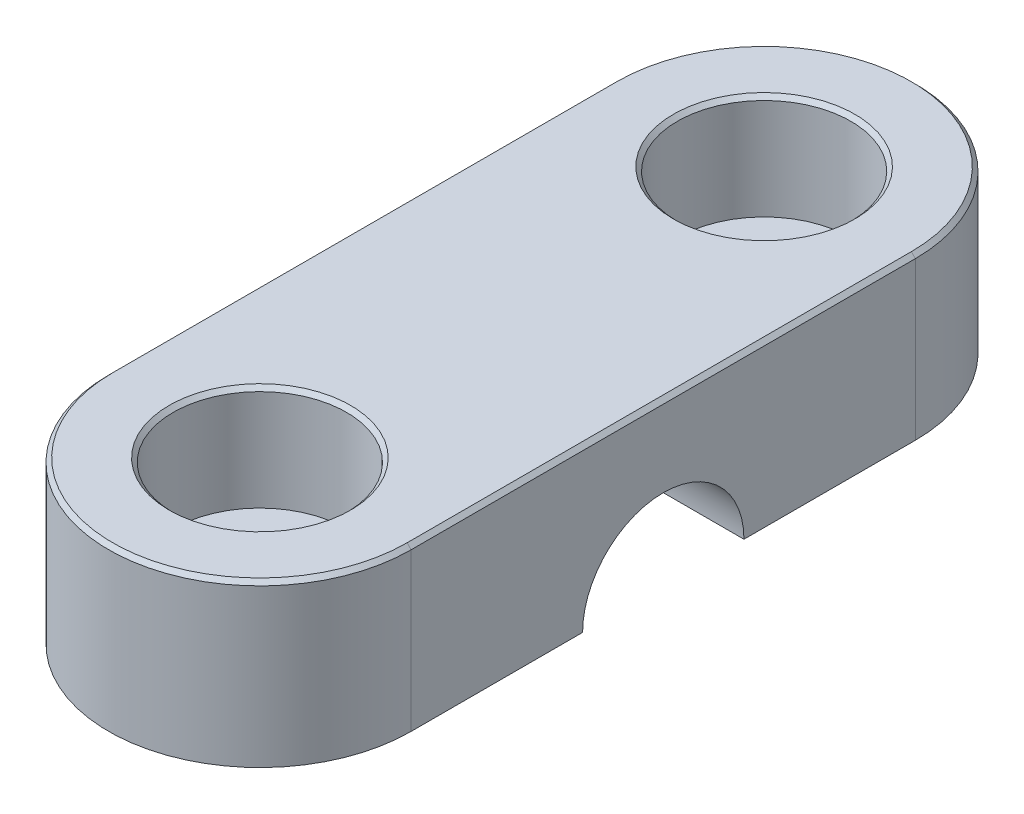
SolidWorks part; units mm, degrees
ref_plane "Front Plane" through (0, 0, 0) normal (0, 0, 1) x (1, 0, 0)
ref_plane "Top Plane" through (0, 0, 0) normal (0, 1, 0) x (1, 0, 0)
ref_plane "Right Plane" through (0, 0, 0) normal (1, 0, 0) x (0, 0, -1)
sketch "Sketch1" plane through (0, 0, 0) normal (0, 1, 0) x (1, 0, 0)
  line L0 (0, 20) -> (0, -20) construction
  line L1 (-7.5, 20) -> (7.5, 20)
  line L2 (-7.5, 20) -> (-7.5, -20)
  line L3 (-7.5, -20) -> (7.5, -20)
  line L4 (7.5, 20) -> (7.5, -20)
  line L5 (-7.5, 20) -> (7.5, -20) construction
  line L6 (-7.5, -20) -> (7.5, 20) construction
  line L7 (-7.5, 0) -> (7.5, 0) construction
  circle A0 centre (0, 12.5) radius 7.5
  circle A1 centre (0, 12.5) radius 2.6
  circle A2 centre (0, -12.5) radius 2.6
  circle A3 centre (0, -12.5) radius 7.5
  point P0 (0, 0)
  dimension "D3" = 5.2
  dimension "D1" = 15
  dimension "D2" = 40
extrude "Boss-Extrude1" add sketch "Sketch1" along normal blind 8 contours A0 A1 | L2 A3 L4 A0 | A3 A2 region at (5.1533, 0, -17.6533) region at (0, 0, 0) region at (0, 0, 5.2121)
sketch "Sketch2" plane through (7.5, 0, 0) normal (1, 0, 0) x (0, 0, -1)
  circle A0 centre (0, 0) radius 4
  point P2 (0, 0)
  point P4 (0, 0)
  dimension "D1" = 8
extrude "Cut-Extrude1" cut sketch "Sketch2" against normal up to next
sketch "Sketch3" plane through (0, 8, 0) normal (0, 1, 0) x (1, 0, 0)
  circle A0 centre (0, 12.5) radius 4.3
  circle A1 centre (0, -12.5) radius 4.3
  dimension "D1" = 8.6
extrude "Cut-Extrude2" cut sketch "Sketch3" against normal blind 5.2
chamfer "Chamfer1" distance 0.2 angle 45 6 edges at (7.5, 8, 0) (0, 8, 20) (-7.5, 8, 0) (0, 8, -20) (0, 8, 16.8) (0, 8, -8.2)
